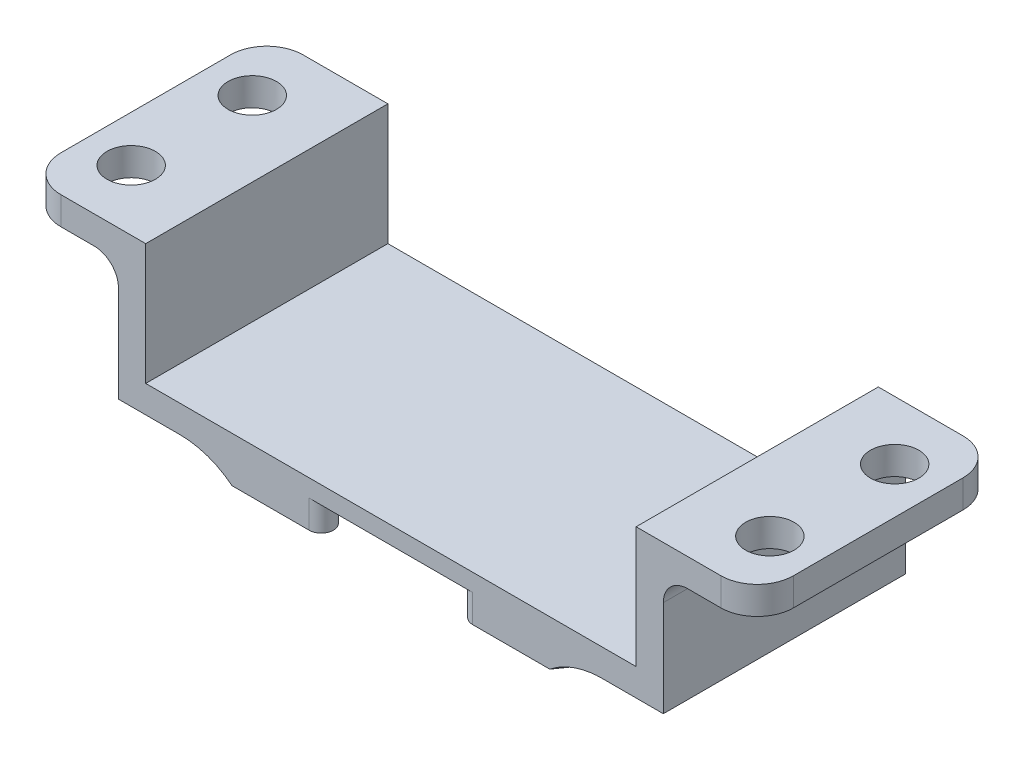
SolidWorks part; units mm, degrees
ref_plane "Front Plane" through (0, 0, 0) normal (0, 0, 1) x (1, 0, 0)
ref_plane "Top Plane" through (0, 0, 0) normal (0, 1, 0) x (1, 0, 0)
ref_plane "Right Plane" through (0, 0, 0) normal (1, 0, 0) x (0, 0, -1)
sketch "Sketch1" plane through (0, 0, 0) normal (0, 1, 0) x (1, 0, 0)
  line L1 (-22.5, -10) -> (22.5, -10)
  line L2 (-22.5, -10) -> (-22.5, 10)
  line L3 (-22.5, 10) -> (22.5, 10)
  line L4 (22.5, -10) -> (22.5, 10)
  line L5 (-22.5, -10) -> (22.5, 10) construction
  line L6 (-22.5, 10) -> (22.5, -10) construction
  point P0 (0, 0)
  dimension "D1" = 45
  dimension "D2" = 20
extrude "Boss-Extrude1" add sketch "Sketch1" along normal blind 2.25
sketch "Sketch2" plane through (0, 2.25, 0) normal (0, 1, 0) x (1, 0, 0)
  line L0 (-22.5, -10) -> (22.5, -10) construction
  line L1 (-22.5, 10) -> (-20.25, 10)
  line L2 (-22.5, 10) -> (-22.5, -10)
  line L3 (-22.5, -10) -> (-20.25, -10)
  line L4 (-20.25, 10) -> (-20.25, -10)
  line L6 (22.5, 10) -> (20.25, 10)
  line L7 (22.5, 10) -> (22.5, -10)
  line L8 (22.5, -10) -> (20.25, -10)
  line L9 (20.25, 10) -> (20.25, -10)
  dimension "D1" = 2.25
  dimension "D2" = 2.25
extrude "Boss-Extrude2" add sketch "Sketch2" along normal blind 10
sketch "Sketch3" plane through (0, 12.25, 0) normal (0, 1, 0) x (1, 0, 0)
  line L1 (-20.25, 10) -> (-30.25, 10)
  line L2 (-20.25, 10) -> (-20.25, -10)
  line L3 (-20.25, -10) -> (-30.25, -10)
  line L4 (-30.25, 10) -> (-30.25, -10)
  line L5 (20.25, 10) -> (30.25, 10)
  line L6 (20.25, 10) -> (20.25, -10)
  line L7 (20.25, -10) -> (30.25, -10)
  line L8 (30.25, 10) -> (30.25, -10)
  dimension "D1" = 10
  dimension "D2" = 10
extrude "Boss-Extrude3" add sketch "Sketch3" against normal blind 2.3
fillet "Fillet1" radius 2 2 edges at (22.5, 9.95, 0) (-22.5, 9.95, 0)
sketch "Sketch4" plane through (0, 12.25, 0) normal (0, 1, 0) x (1, 0, 0)
  line L0 (-69.1199, 0) -> (76.1978, 0) construction
  line L1 (-26.45, 17.4182) -> (-26.45, -16.8653) construction
  line L2 (26.45, 13.8793) -> (26.45, -18.7453) construction
  line L3 (-30.25, 10) -> (-30.25, -10) construction
  line L4 (30.25, -10) -> (30.25, 10) construction
  circle A0 centre (26.45, 5.1528) radius 2
  circle A1 centre (26.45, -5.1528) radius 2
  circle A2 centre (-26.45, 5) radius 2
  circle A3 centre (-26.45, -5) radius 2
  dimension "D3" = 4
  dimension "D1" = 3.8
  dimension "D2" = 3.8
  dimension "D4" = 5
extrude "Cut-Extrude1" cut sketch "Sketch4" against normal through all
sketch "Sketch5" plane through (0, 0, 0) normal (0, -1, 0) x (1, 0, 0)
  line L4 (22.5, -10) -> (22.5, 10)
  line L5 (22.5, 10) -> (-22.5, 10)
  line L6 (-22.5, 10) -> (-22.5, -10)
  line L7 (-22.5, -10) -> (22.5, -10)
  line L9 (13.1244, 10) -> (-13.1244, 10)
  line L11 (-13.1244, -10) -> (13.1244, -10)
  arc A0 (-13.1244, 10) -> (-13.1244, -10) centre (0, 0) ccw
  arc A1 (13.1244, -10) -> (13.1244, 10) centre (0, 0) ccw
  dimension "D1" = 33
  dimension "D2" = 0
extrude "Boss-Extrude5" add sketch "Sketch5" along normal blind 1.5
sketch "Sketch6" plane through (0, -1.5, 0) normal (0, -1, 0) x (1, 0, 0)
  circle A0 centre (0, 0) radius 10.25
  dimension "D1" = 20.5
extrude "Cut-Extrude2" cut sketch "Sketch6" against normal blind 2.3
fillet "Fillet2" radius 5 2 edges at (16.5, 0, 0) (-16.5, 0, 0)
fillet "Fillet3" radius 1 4 edges at (2.25, -0.35, 10) (-2.25, -0.35, 10) (2.25, -0.35, -10) (-2.25, -0.35, -10)
fillet "Fillet4" radius 3 4 edges at (30.25, 11.1, 10) (30.25, 11.1, -10) (-30.25, 11.1, 10) (-30.25, 11.1, -10)
